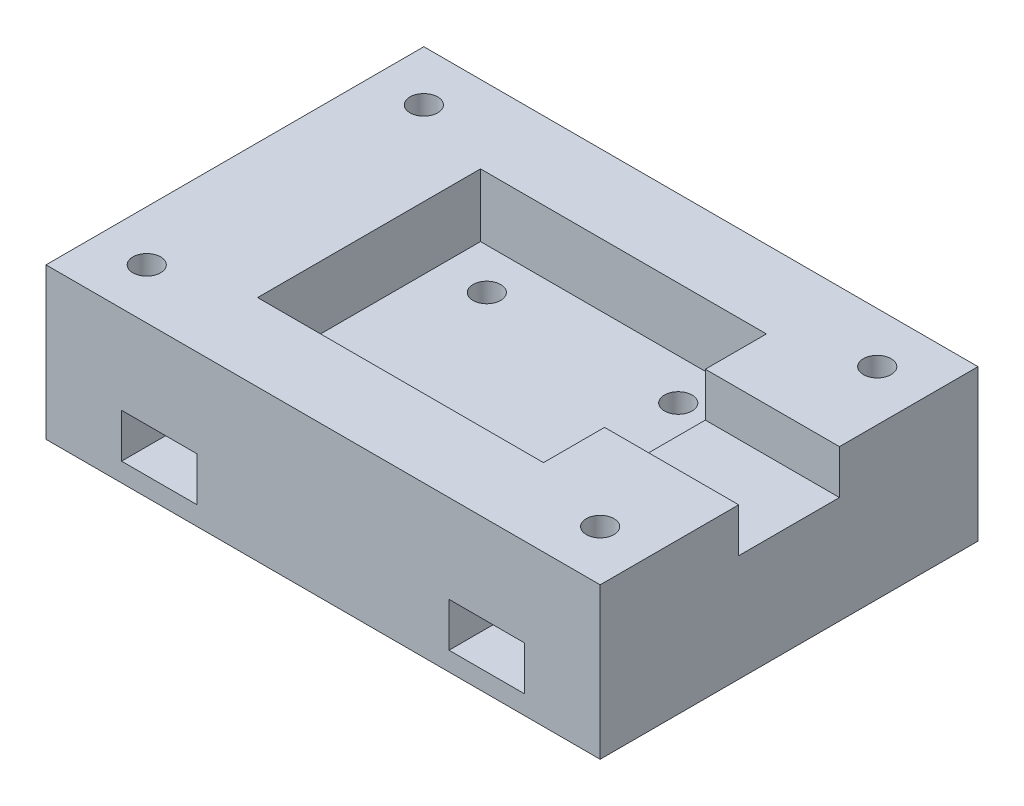
SolidWorks part; units mm, degrees
ref_plane "Front Plane" through (0, 0, 0) normal (0, 0, 1) x (1, 0, 0)
ref_plane "Top Plane" through (0, 0, 0) normal (0, 1, 0) x (1, 0, 0)
ref_plane "Right Plane" through (0, 0, 0) normal (1, 0, 0) x (0, 0, -1)
sketch "Sketch1" plane through (0, 0, 0) normal (0, 1, 0) x (1, 0, 0)
  line L1 (-22, -15) -> (22, -15)
  line L2 (-22, -15) -> (-22, 15)
  line L3 (-22, 15) -> (22, 15)
  line L4 (22, -15) -> (22, 15)
  line L5 (-22, -15) -> (22, 15) construction
  line L6 (-22, 15) -> (22, -15) construction
  point P0 (0, 0)
  dimension "D1" = 44
  dimension "D2" = 30
extrude "Pod Body" add sketch "Sketch1" along normal blind 12
ref_plane "Pod Top" through (0, 12, 0) normal (0, 1, 0) x (1, 0, 0)
sketch "Sketch2" plane through (0, 12, 0) normal (0, 1, 0) x (1, 0, 0)
  line L1 (-11.35, -8.85) -> (11.35, -8.85)
  line L2 (-11.35, -8.85) -> (-11.35, 8.85)
  line L3 (-11.35, 8.85) -> (11.35, 8.85)
  line L4 (11.35, -8.85) -> (11.35, 8.85)
  line L5 (-11.35, -8.85) -> (11.35, 8.85) construction
  line L6 (-11.35, 8.85) -> (11.35, -8.85) construction
  point P0 (0, 0)
  dimension "D1" = 22.7
  dimension "D2" = 17.7
extrude "Board Pocket" cut sketch "Sketch2" against normal blind 5
sketch "Sketch3" plane through (0, 12, 0) normal (0, 1, 0) x (1, 0, 0)
  circle A0 centre (-7.6, 5.6) radius 1.1
  circle A1 centre (7.6, 5.6) radius 1.1
extrude "Board Pilot Holes" cut sketch "Sketch3" against normal blind 9
sketch "Sketch4" plane through (0, 12, 0) normal (0, 1, 0) x (1, 0, 0)
  circle A0 centre (-18, -11) radius 1.1
  circle A1 centre (-18, 11) radius 1.1
  circle A2 centre (18, -11) radius 1.1
  circle A3 centre (18, 11) radius 1.1
extrude "Lid Pilot Holes" cut sketch "Sketch4" against normal blind 8
sketch "Sketch5" plane through (0, 12, 0) normal (0, 1, 0) x (1, 0, 0)
  line L1 (10.35, -4) -> (23, -4)
  line L2 (10.35, -4) -> (10.35, 4)
  line L3 (10.35, 4) -> (23, 4)
  line L4 (23, -4) -> (23, 4)
extrude "Cable Exit" cut sketch "Sketch5" against normal blind 3.5
sketch "Sketch7" plane through (0, 0, 0) normal (0, 0, 1) x (1, 0, 0)
  line L0 (-12, 5) -> (-6, 5) construction
  line L1 (-16, 1.5) -> (-10, 1.5)
  line L2 (-16, 1.5) -> (-16, 5)
  line L3 (-16, 5) -> (-10, 5)
  line L4 (-10, 1.5) -> (-10, 5)
  line L5 (6, 1.5) -> (12, 1.5) construction
  line L6 (10, 1.5) -> (16, 1.5)
  line L7 (10, 1.5) -> (10, 5)
  line L8 (10, 5) -> (16, 5)
  line L9 (16, 1.5) -> (16, 5)
extrude "Strap Slots" cut sketch "Sketch7" against normal through all and the other way through all
equation "\"PodL\" = 44.0"
equation "\"PodW\" = 30.0"
equation "\"PodH\" = 12.0"
equation "\"BoardL\" = 21.5"
equation "\"BoardW\" = 16.5"
equation "\"Clear\" = 0.6"
equation "\"PocketD\" = 5.0"
equation "\"D1@Sketch1\" = \"PodL\""
equation "\"D2@Sketch1\" = \"PodW\""
equation "\"HoleSpacing\" = 15.2"
equation "\"HoleOffset\" = 5.6"
equation "\"PilotD\" = 2.2"
equation "\"FloorHoleD\" = 4.0"
equation "\"LidInset\" = 4.0"
equation "\"StrapX\" = 13.0"
equation "\"StrapW\" = 6.0"
equation "\"StrapT\" = 3.5"
equation "\"StrapZ0\" = 1.5"
equation "\"CableW\" = 8.0"
equation "\"D1@Pod Top\" = \"PodH\""
equation "\"D1@Sketch2\" = \"BoardL\" + 2 * \"Clear\""
equation "\"D2@Sketch2\" = \"BoardW\" + 2 * \"Clear\""
equation "\"D1@Board Pocket\" = \"PocketD\""
equation "\"D1@Board Pilot Holes\" = \"PocketD\" + \"FloorHoleD\""
